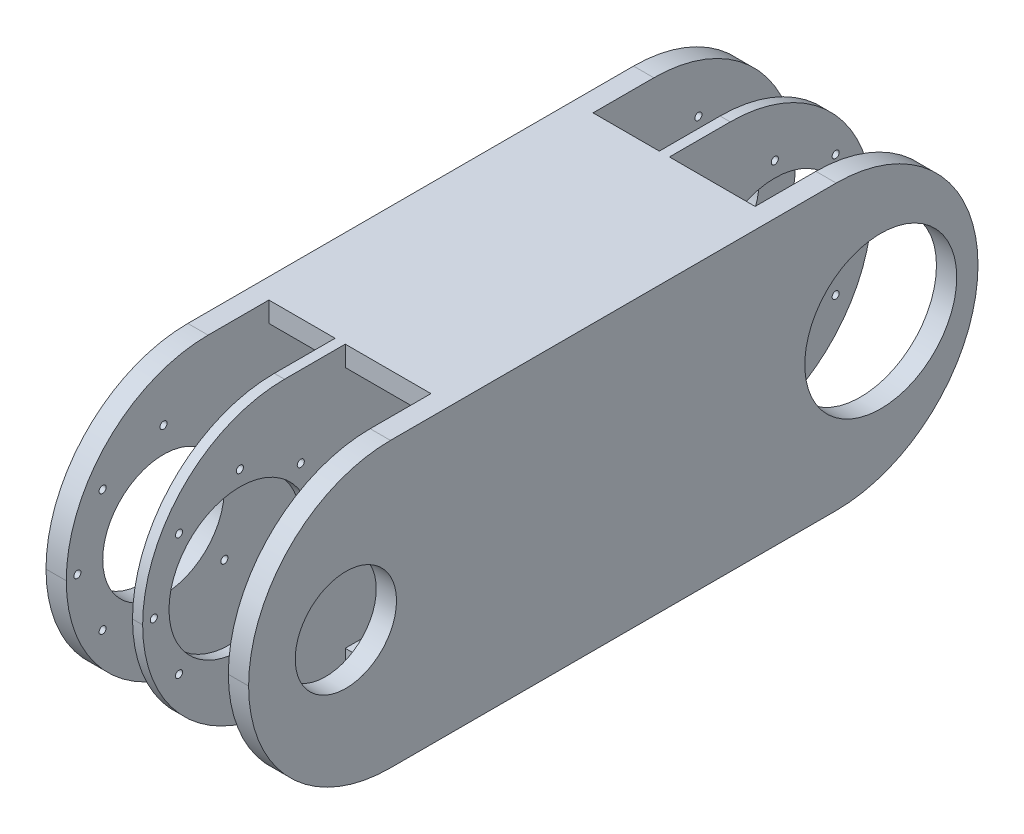
SolidWorks part; units mm, degrees
ref_plane "前视基准面" through (0, 0, 0) normal (0, 0, 1) x (1, 0, 0)
ref_plane "上视基准面" through (0, 0, 0) normal (0, 1, 0) x (1, 0, 0)
ref_plane "右视基准面" through (0, 0, 0) normal (1, 0, 0) x (0, 0, -1)
sketch "草图1" plane through (0, 0, 0) normal (0, 0, 1) x (1, 0, 0)
  line L1 (-36.2442, 10.9365) -> (6.0558, 10.9365)
  line L2 (-36.2442, 10.9365) -> (-36.2442, -129.0635)
  line L3 (-36.2442, -129.0635) -> (6.0558, -129.0635)
  line L4 (6.0558, 10.9365) -> (6.0558, -129.0635)
  line L5 (-15.0942, -129.0635) -> (-15.0942, 10.9365) construction
  line L6 (-36.2442, -59.0635) -> (6.0558, -59.0635) construction
  line L7 (-41.2442, 10.9365) -> (16.0558, 10.9365)
  line L8 (-41.2442, 10.9365) -> (-41.2442, -129.0635)
  line L9 (-41.2442, -129.0635) -> (16.0558, -129.0635)
  line L10 (16.0558, 10.9365) -> (16.0558, -129.0635)
  line L11 (-12.5942, -129.0635) -> (-12.5942, 10.9365) construction
  line L12 (-41.2442, -59.0635) -> (16.0558, -59.0635) construction
  line L13 (-36.2442, 0.9365) -> (6.0558, 0.9365)
  line L14 (-36.2442, 0.9365) -> (-36.2442, -119.0635)
  line L15 (-36.2442, -119.0635) -> (6.0558, -119.0635)
  line L16 (6.0558, 0.9365) -> (6.0558, -119.0635)
  line L17 (-15.0942, -119.0635) -> (-15.0942, 0.9365) construction
  line L18 (-36.2442, -59.0635) -> (6.0558, -59.0635) construction
  point P0 (-15.0942, -59.0635)
  point P4 (-12.5942, -59.0635)
  point P9 (-15.0942, -59.0635)
  dimension "D1" = 42.3
  dimension "D2" = 140
  dimension "D3" = 0
  dimension "D4" = 0
  dimension "D5" = 10
  dimension "D6" = 5
  dimension "D7" = 0
  dimension "D8" = 0
  dimension "D9" = 10
  dimension "D10" = 10
extrude "凸台-拉伸3" add sketch "草图1" along normal blind 240 contours L2 L13 L4 L1 | L8 L9 L2 L7 | L10 L7 L4 L9 | L15 L2 L3 L4 region at (-15.0942, 5.9365, 0) region at (-38.7442, -59.0635, 0) region at (11.0558, -59.0635, 0) region at (-15.0942, -124.0635, 0)
sketch "草图2" plane through (0, 0, 240) normal (0, 0, 1) x (1, 0, 0)
  line L0 (-41.2442, 10.9365) -> (16.0558, 10.9365) construction
  line L1 (-36.2442, 10.9365) -> (6.0558, 10.9365)
  line L2 (-36.2442, 10.9365) -> (-36.2442, -129.0635)
  line L3 (-36.2442, -129.0635) -> (6.0558, -129.0635)
  line L4 (6.0558, 10.9365) -> (6.0558, -129.0635)
  line L5 (-15.0942, -129.0635) -> (-15.0942, 10.9365) construction
  line L6 (-36.2442, -59.0635) -> (6.0558, -59.0635) construction
  line L7 (-41.2442, -129.0635) -> (16.0558, -129.0635) construction
  line L8 (6.0558, 0.9365) -> (6.0558, -119.0635) construction
  line L9 (-36.2442, 0.9365) -> (-36.2442, -119.0635) construction
  point P0 (-15.0942, -59.0635)
  dimension "D1" = 0
  dimension "D2" = 0
  dimension "D3" = 0
  dimension "D4" = 0
extrude "切除-拉伸1" cut sketch "草图2" against normal blind 100
sketch "草图3" plane through (0, -129.0635, 0) normal (0, -1, 0) x (1, 0, 0)
  line L0 (-41.2442, 0) -> (16.0558, 0) construction
  line L1 (-83.9442, 240) -> (-41.2442, 240)
  line L2 (-83.9442, 240) -> (-83.9442, 0)
  line L3 (-83.9442, 0) -> (-41.2442, 0)
  line L4 (-41.2442, 240) -> (-41.2442, 0)
  line L5 (-62.5942, 0) -> (-62.5942, 240) construction
  line L6 (-83.9442, 120) -> (-41.2442, 120) construction
  line L7 (-41.2442, 240) -> (-41.2442, 0) construction
  line L8 (16.0558, 240) -> (16.0558, 0) construction
  line L9 (-41.2442, 240) -> (-36.2442, 240) construction
  point P0 (-62.5942, 120)
  dimension "D1" = 0
  dimension "D2" = 0
  dimension "D3" = 100
  dimension "D4" = 0
extrude "凸台-拉伸4" add sketch "草图3" against normal blind 140
sketch "草图4" plane through (0, 0, 240) normal (0, 0, 1) x (1, 0, 0)
  line L0 (-36.2442, 10.9365) -> (-36.2442, -129.0635) construction
  line L1 (-73.9442, 0.9365) -> (-41.2442, 0.9365)
  line L2 (-73.9442, 0.9365) -> (-73.9442, -119.0635)
  line L3 (-73.9442, -119.0635) -> (-41.2442, -119.0635)
  line L4 (-41.2442, 0.9365) -> (-41.2442, -119.0635)
  line L5 (-57.5942, -119.0635) -> (-57.5942, 0.9365) construction
  line L6 (-73.9442, -59.0635) -> (-41.2442, -59.0635) construction
  line L7 (-83.9442, -129.0635) -> (-36.2442, -129.0635) construction
  line L8 (-36.2442, 0.9365) -> (6.0558, 0.9365) construction
  line L9 (-83.9442, 10.9365) -> (-83.9442, -129.0635) construction
  point P0 (-57.5942, -59.0635)
  dimension "D1" = 5
  dimension "D2" = 10
  dimension "D3" = 0
  dimension "D4" = 10
extrude "切除-拉伸2" cut sketch "草图4" against normal up to next
sketch "草图5" plane through (-83.9442, 0, 0) normal (-1, 0, 0) x (0, 0, 1)
  line L0 (240, 10.9365) -> (0, 10.9365) construction
  line L1 (240, -119.0635) -> (240, 0.9365) construction
  circle A0 centre (192, -59.0635) radius 42.5
  circle A2 centre (192, -59.0635) radius 30
  circle A15 centre (149.5, -59.0635) radius 1.75
  circle A16 centre (161.948, -29.0114) radius 1.75
  circle A17 centre (192, -16.5635) radius 1.75
  circle A18 centre (222.052, -29.0114) radius 1.75
  circle A19 centre (234.5, -59.0635) radius 1.75
  circle A20 centre (222.052, -89.1155) radius 1.75
  circle A21 centre (192, -101.5635) radius 1.75
  circle A22 centre (161.948, -89.1155) radius 1.75
  point P25 (192, -59.0635)
  point P26 (190, -59.0635)
  dimension "D1" = 85
  dimension "D3" = 48
  dimension "D4" = 60
  dimension "D5" = 8
  dimension "D2" = 70
sketch "草图6" plane through (-41.2442, 0, 0) normal (-1, 0, 0) x (0, 0, 1)
  line L0 (240, 10.9365) -> (0, 10.9365) construction
  line L1 (240, -119.0635) -> (240, 0.9365) construction
  circle A0 centre (192, -59.0635) radius 42.5
  circle A1 centre (192, -59.0635) radius 35
  circle A2 centre (234.5, -59.0635) radius 1.75
  circle A3 centre (222.052, -89.1155) radius 1.75
  circle A4 centre (192, -101.5635) radius 1.75
  circle A5 centre (161.948, -89.1155) radius 1.75
  circle A6 centre (149.5, -59.0635) radius 1.75
  circle A7 centre (161.948, -29.0114) radius 1.75
  circle A8 centre (192, -16.5635) radius 1.75
  circle A9 centre (222.052, -29.0114) radius 1.75
  point P26 (192, -59.0635)
  dimension "D1" = 85
  dimension "D4" = 8
  dimension "D2" = 70
  dimension "D3" = 48
sketch "草图7" plane through (0, 0, 240) normal (0, 0, 1) x (1, 0, 0)
  line L0 (-41.2442, -119.0635) -> (-41.2442, 0.9365) construction
  line L1 (-73.9442, 10.9365) -> (-41.2442, 10.9365)
  line L2 (-73.9442, 10.9365) -> (-73.9442, -129.0635)
  line L3 (-73.9442, -129.0635) -> (-41.2442, -129.0635)
  line L4 (-41.2442, 10.9365) -> (-41.2442, -129.0635)
  line L5 (-57.5942, -129.0635) -> (-57.5942, 10.9365) construction
  line L6 (-73.9442, -59.0635) -> (-41.2442, -59.0635) construction
  line L7 (-73.9442, 0.9365) -> (-73.9442, -119.0635) construction
  line L8 (-73.9442, -119.0635) -> (-41.2442, -119.0635) construction
  line L10 (-83.9442, 10.9365) -> (-36.2442, 10.9365) construction
  point P0 (-57.5942, -59.0635)
  dimension "D1" = 0
  dimension "D2" = 0
  dimension "D3" = 10
  dimension "D4" = 0
extrude "切除-拉伸6" cut sketch "草图7" against normal blind 100
fillet "圆角2" radius 70 6 edges at (11.0558, 10.9365, 240) (-38.7442, 10.9365, 240) (-78.9442, 10.9365, 240) (11.0558, -129.0635, 240) (-38.7442, -129.0635, 240) (-78.9442, -129.0635, 240)
extrude "切除-拉伸7" cut sketch "草图6" against normal blind 10 contours A1 | A6 | A7 | A8 | A9 | A2 | A3 | A4 | A5 region at (-41.2442, -59.0635, 192)
extrude "切除-拉伸8" cut sketch "草图5" against normal blind 10 contours A2 | A16 | A15 | A22 | A21 | A20 | A19 | A18 | A17 region at (-83.9442, -59.0635, 192)
sketch "草图8" plane through (0, 0, 0) normal (0, 0, -1) x (-1, 0, 0)
  line L0 (83.9442, 10.9365) -> (-16.0558, 10.9365) construction
  line L1 (-16.0558, 10.9365) -> (-6.0558, 10.9365)
  line L2 (-16.0558, 10.9365) -> (-16.0558, -129.0635)
  line L3 (-16.0558, -129.0635) -> (-6.0558, -129.0635)
  line L4 (-6.0558, 10.9365) -> (-6.0558, -129.0635)
  line L5 (-11.0558, -129.0635) -> (-11.0558, 10.9365) construction
  line L6 (-16.0558, -59.0635) -> (-6.0558, -59.0635) construction
  line L7 (-16.0558, 10.9365) -> (-16.0558, -129.0635) construction
  line L8 (-6.0558, 0.9365) -> (-6.0558, -119.0635) construction
  line L9 (83.9442, -129.0635) -> (-16.0558, -129.0635) construction
  line L10 (73.9442, 10.9365) -> (73.9442, -129.0635)
  line L11 (73.9442, 10.9365) -> (83.9442, 10.9365)
  line L12 (83.9442, 10.9365) -> (83.9442, -129.0635)
  line L13 (73.9442, -129.0635) -> (83.9442, -129.0635)
  point P0 (-11.0558, -59.0635)
  dimension "D1" = 0
  dimension "D2" = 0
  dimension "D3" = 0
  dimension "D4" = 0
  dimension "D5" = 2
extrude "凸台-拉伸5" add sketch "草图8" along normal blind 110
fillet "圆角4" radius 60 4 edges at (-78.9442, 10.9365, -110) (-78.9442, -129.0635, -110) (11.0558, -129.0635, -110) (11.0558, 10.9365, -110)
sketch "草图17" plane through (-83.9442, 0, 0) normal (-1, 0, 0) x (0, 0, 1)
  circle A0 centre (192, -59.0635) radius 25
extrude "切除-拉伸13" cut sketch "草图17" against normal blind 139
sketch "草图18" plane through (16.0558, 0, 0) normal (1, 0, 0) x (0, 0, -1)
  line L0 (-60, 10.9365) -> (-60, -129.0635)
  line L1 (-170, 10.9365) -> (50, 10.9365) construction
  line L2 (-170, -129.0635) -> (50, -129.0635) construction
  line L4 (-60, 86.3555) -> (264.5033, 86.3555)
  line L5 (-60, 86.3555) -> (-60, -152.3645)
  line L6 (-60, -152.3645) -> (264.5033, -152.3645)
  line L7 (264.5033, 86.3555) -> (264.5033, -152.3645)
  line L8 (102.2516, -152.3645) -> (102.2516, 86.3555) construction
  line L9 (-60, -33.0045) -> (264.5033, -33.0045) construction
  point P6 (102.2516, -33.0045)
  line M7 (-170, -129.0635) -> (50, -129.0635)
  arc M8 (50, -129.0635) -> (110, -69.0635) centre (50, -69.0635) ccw
  line M9 (110, -69.0635) -> (110, -49.0635)
  arc M10 (110, -49.0635) -> (50, 10.9365) centre (50, -49.0635) ccw
  line M11 (50, 10.9365) -> (-170, 10.9365)
  dimension "D1" = 0
extrude "切除-拉伸14" cut sketch "草图18" against normal blind 110 contours L7 L4 L5 L6 M11 M10 M9 M8 M7 | L0 M11 M7 M8 M9 M10 region at (16.0558, -59.0635, -20.029) region at (16.0558, -22.5003, -135.3948)
mirror "镜向2" about plane through (-93.9442, 0, 60) normal (0, 0, 1) of bodies 119
sketch "草图19" plane through (16.0558, 0, 0) normal (1, 0, 0) x (0, 0, -1)
  circle A0 centre (72, -59.0635) radius 37.5
extrude "切除-拉伸15" cut sketch "草图19" against normal blind 14
